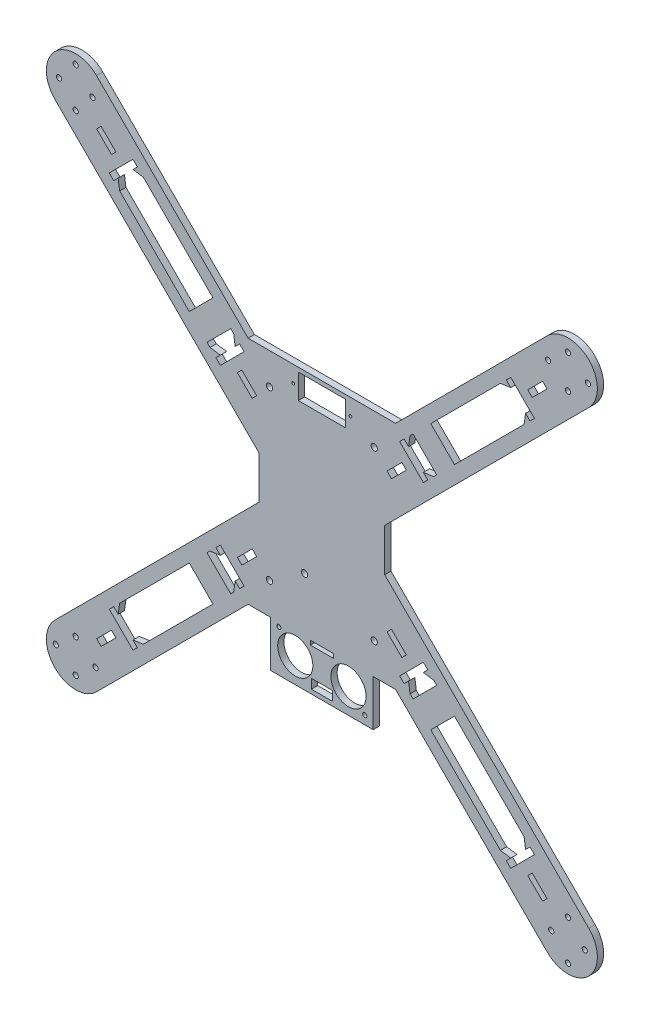
SolidWorks part; units mm, degrees
material "Custom Plastic"
ref_plane "Front Plane" through (0, 0, 0) normal (0, 0, 1) x (1, 0, 0)
ref_plane "Top Plane" through (0, 0, 0) normal (0, 1, 0) x (1, 0, 0)
ref_plane "Right Plane" through (0, 0, 0) normal (1, 0, 0) x (0, 0, -1)
sketch "Sketch1" plane through (0, 0, 0) normal (0, 0, 1) x (1, 0, 0)
  line L0 (117.5, 117.5) -> (-117.5, 117.5) construction
  line L1 (-117.5, 117.5) -> (117.5, -117.5) construction
  line L2 (117.5, -117.5) -> (-117.5, -117.5) construction
  line L3 (-117.5, -117.5) -> (117.5, 117.5) construction
  line L4 (117.5, 117.5) -> (117.5, -117.5) construction
  line L5 (-117.5, 117.5) -> (-117.5, -117.5) construction
  line L6 (0, 117.5) -> (0, -117.5) construction
  line L7 (35.201, 55) -> (-35.201, 55)
  line L8 (-30, 55) -> (30, 55) construction
  line L9 (-35.201, 55) -> (-107.6005, 127.3995)
  line L10 (-127.3995, 107.6005) -> (-30, 10.201)
  line L11 (-117.5, 0) -> (117.5, 0) construction
  line L12 (-30, 10.201) -> (-30, -10.201)
  line L13 (30, 55) -> (30, -55) construction
  line L14 (30, -55) -> (-30, -55) construction
  line L15 (-30, -55) -> (-30, 55) construction
  line L16 (30, 55) -> (-30, -55) construction
  line L17 (-24.5, -55) -> (-24.5, -77)
  line L18 (-127.3995, -107.6005) -> (-30, -10.201)
  line L19 (-24.5, -77) -> (24.5, -77)
  line L20 (-35.201, -55) -> (-107.6005, -127.3995)
  line L21 (35.201, -55) -> (24.5, -55)
  line L22 (35.201, -55) -> (107.6005, -127.3995)
  line L23 (127.3995, -107.6005) -> (30, -10.201)
  line L24 (30, 10.201) -> (30, -10.201)
  line L25 (127.3995, 107.6005) -> (30, 10.201)
  line L26 (35.201, 55) -> (107.6005, 127.3995)
  line L27 (24.5, -55) -> (24.5, -77)
  line L28 (-24.5, -55) -> (-35.201, -55)
  arc A0 (-107.6005, 127.3995) -> (-127.3995, 107.6005) centre (-117.5, 117.5) ccw
  arc A12 (-107.6005, -127.3995) -> (-127.3995, -107.6005) centre (-117.5, -117.5) cw
  arc A16 (107.6005, -127.3995) -> (127.3995, -107.6005) centre (117.5, -117.5) ccw
  arc A24 (107.6005, 127.3995) -> (127.3995, 107.6005) centre (117.5, 117.5) cw
  point P3 (0, 0)
  point P18 (0, 0)
  point P21 (0, -77)
  point P33 (-117.5, 117.5)
  point P34 (-30, 0)
  point P65 (0, -55)
  point P80 (0, 55)
  dimension "D3" = 14
  dimension "D8" = 24.5
  dimension "D7" = 22
  dimension "D1" = 235
  dimension "D2" = 235
  dimension "D4" = 60
  dimension "D5" = 110
  dimension "D6" = 28
extrude "Boss-Extrude1" add sketch "Sketch1" against normal blind 3
sketch "Sketch4" plane through (0, 0, 0) normal (0, 0, 1) x (1, 0, 0)
  line L0 (0, 0) -> (0, 55) construction
  line L1 (35.201, 55) -> (-35.201, 55) construction
  line L2 (0, 0) -> (-30, 0) construction
  line L3 (-30, 10.201) -> (-30, -10.201) construction
  line L4 (-30, 0) -> (-30, 10.201) construction
  line L5 (-30, 10.201) -> (-127.3995, 107.6005) construction
  line L6 (-35.201, 55) -> (-107.6005, 127.3995) construction
  line L7 (-107.6005, 127.3995) -> (-127.3995, 107.6005) construction
  line L8 (-117.5, 127) -> (-117.5, 108) construction
  line L9 (-125.5, 117.5) -> (-109.5, 117.5) construction
  circle A4 centre (-25, 40) radius 1.5
  circle A9 centre (-25, -40) radius 1.5
  circle A18 centre (25, -40) radius 1.5
  circle A19 centre (25, 40) radius 1.5
  circle A20 centre (-117.5, 127) radius 1.25
  circle A21 centre (-117.5, 108) radius 1.25
  circle A22 centre (-125.5, 117.5) radius 1.25
  circle A23 centre (-109.5, 117.5) radius 1.25
  circle A24 centre (117.5, 109.5) radius 1.25
  circle A25 centre (108, 117.5) radius 1.25
  circle A26 centre (117.5, 125.5) radius 1.25
  circle A27 centre (127, 117.5) radius 1.25
  circle A28 centre (109.5, -117.5) radius 1.25
  circle A29 centre (117.5, -108) radius 1.25
  circle A30 centre (125.5, -117.5) radius 1.25
  circle A31 centre (117.5, -127) radius 1.25
  circle A32 centre (-117.5, -109.5) radius 1.25
  circle A33 centre (-108, -117.5) radius 1.25
  circle A34 centre (-117.5, -125.5) radius 1.25
  circle A35 centre (-127, -117.5) radius 1.25
  point P16 (-117.5, 117.5)
  point P19 (-117.5, 117.5)
  point P26 (-117.5, 117.5)
  point P62 (0, 0)
  dimension "D1" = 45
  dimension "D6" = 3
  dimension "D4" = 2.5
  dimension "D2" = 19
  dimension "D7" = 15
  dimension "D8" = 5
  dimension "D3" = 16
extrude "Cut-Extrude1" cut sketch "Sketch4" against normal blind 3
sketch "Sketch5" plane through (0, 0, 0) normal (0, 0, 1) x (1, 0, 0)
  line L7 (-11.25, 53) -> (-11.25, 41.2)
  line L8 (-11.25, 41.2) -> (11.25, 41.2)
  line L9 (11.25, 41.2) -> (11.25, 53)
  line L10 (11.25, 53) -> (-11.25, 53)
  line L12 (0, 53) -> (0, 41.2) construction
  line L13 (-13.65, 47.1) -> (13.65, 47.1) construction
  line L14 (35.201, 55) -> (-35.201, 55) construction
  circle A2 centre (-13.65, 47.1) radius 0.65
  circle A3 centre (13.65, 47.1) radius 0.65
  point P20 (0, 47.1)
  point P21 (0, 47.1)
  point P26 (0, 55)
  dimension "D8" = 1.3
  dimension "D9" = 1.3
  dimension "D10" = 27.3
  dimension "D11" = 22.5
  dimension "D12" = 11.8
  dimension "D13" = 2
extrude "Cut-Extrude2" cut sketch "Sketch5" against normal blind 3
sketch "Sketch6" plane through (0, 0, 0) normal (0, 0, 1) x (1, 0, 0)
  line L1 (-11.25, 41.2) -> (11.25, 41.2) construction
  circle A0 centre (-8.25, -28.8) radius 1.5
  dimension "D3" = 3
  dimension "D1" = 70
  dimension "D2" = 3
extrude "Cut-Extrude3" cut sketch "Sketch6" against normal blind 3
sketch "Sketch7" plane through (0, 0, 0) normal (0, 0, 1) x (1, 0, 0)
  line L0 (-22.5, -55) -> (-22.5, -75) construction
  line L5 (-22.5, -75) -> (22.5, -75) construction
  line L6 (22.5, -75) -> (22.5, -55) construction
  line L7 (22.5, -55) -> (-22.5, -55) construction
  line L8 (0, -55) -> (0, -75) construction
  line L9 (-12.7, -65) -> (0, -65) construction
  line L10 (-24.5, -77) -> (24.5, -77) construction
  line L11 (-24.5, -55) -> (-24.5, -77) construction
  line L12 (-5.5, -55) -> (-5.5, -57)
  line L13 (-5.5, -57) -> (5.5, -57)
  line L15 (5.5, -55) -> (-5.5, -55)
  line L16 (-5, -75) -> (-5, -70.5)
  line L17 (-5, -70.5) -> (5, -70.5)
  line L21 (5, -75) -> (-5, -75)
  line L22 (5.5, -55) -> (5.5, -57)
  line L23 (5, -75) -> (5, -70.5)
  circle A5 centre (-20.5, -57) radius 1
  circle A6 centre (-12.7, -65) radius 8.4
  circle A7 centre (12.7, -65) radius 8.4
  circle A8 centre (20.5, -73) radius 1
  point P25 (0, -57)
  point P26 (0, -70.5)
  dimension "D3" = 2
  dimension "D6" = 20
  dimension "D13" = 5
  dimension "D5" = 45
  dimension "D1" = 2
  dimension "D4" = 16.8
  dimension "D14" = 2
  dimension "D2" = 2
  dimension "D7" = 2
  dimension "D8" = 2
  dimension "D9" = 12.7
  dimension "D10" = 5.5
  dimension "D11" = 2
  dimension "D12" = 4.5
  dimension "D15" = 2
  dimension "D16" = 2
extrude "Cut-Extrude4" cut sketch "Sketch7" against normal blind 3
sketch "Sketch8" plane through (0, 0, 0) normal (0, 0, 1) x (1, 0, 0)
  line L0 (101.4792, -90.1655) -> (90.1655, -101.4792)
  line L1 (90.1655, -101.4792) -> (88.0442, -99.3579)
  line L2 (37.1325, -48.4462) -> (48.4462, -37.1325)
  line L3 (48.4462, -37.1325) -> (50.5675, -39.2538)
  line L4 (105.7218, -85.9228) -> (85.9228, -105.7218) construction
  line L5 (127.3995, -107.6005) -> (30, -10.201) construction
  line L6 (35.201, -55) -> (107.6005, -127.3995) construction
  line L7 (40.3144, -38.1931) -> (38.1931, -40.3144)
  line L8 (117.5, -109.5) -> (109.5, -117.5) construction
  line L9 (38.1931, -40.3144) -> (31.1221, -33.2434)
  line L10 (50.5675, 39.2538) -> (48.4462, 37.1325)
  line L11 (31.1221, -33.2434) -> (33.2434, -31.1221)
  line L12 (33.2434, -31.1221) -> (40.3144, -38.1931)
  line L13 (42.7893, -42.7893) -> (39.2538, -39.2538) construction
  line L14 (35.201, -55) -> (107.6005, -127.3995) construction
  line L15 (100.4185, -98.2972) -> (98.2972, -100.4185)
  line L16 (98.2972, -100.4185) -> (105.3683, -107.4896)
  line L17 (105.3683, -107.4896) -> (107.4896, -105.3683)
  line L18 (107.4896, -105.3683) -> (100.4185, -98.2972)
  line L19 (99.3579, -99.3579) -> (95.8223, -95.8223) construction
  line L20 (-101.4792, -90.1655) -> (-99.3579, -88.0442)
  line L21 (-100.4185, -98.2972) -> (-107.4896, -105.3683)
  line L22 (-107.4896, -105.3683) -> (-105.3683, -107.4896)
  line L23 (-105.3683, -107.4896) -> (-98.2972, -100.4185)
  line L24 (-98.2972, -100.4185) -> (-100.4185, -98.2972)
  line L25 (-90.1655, -101.4792) -> (-101.4792, -90.1655)
  line L26 (-37.1325, -48.4462) -> (-39.2538, -50.5675)
  line L27 (-48.4462, -37.1325) -> (-37.1325, -48.4462)
  line L28 (-38.1931, -40.3144) -> (-40.3144, -38.1931)
  line L29 (-31.1221, -33.2434) -> (-38.1931, -40.3144)
  line L30 (-40.3144, -38.1931) -> (-33.2434, -31.1221)
  line L31 (-33.2434, -31.1221) -> (-31.1221, -33.2434)
  line L32 (-90.1655, 101.4792) -> (-88.0442, 99.3579)
  line L33 (-98.2972, 100.4185) -> (-105.3683, 107.4896)
  line L34 (-105.3683, 107.4896) -> (-107.4896, 105.3683)
  line L35 (-107.4896, 105.3683) -> (-100.4185, 98.2972)
  line L36 (-100.4185, 98.2972) -> (-98.2972, 100.4185)
  line L37 (-101.4792, 90.1655) -> (-90.1655, 101.4792)
  line L38 (-48.4462, 37.1325) -> (-50.5675, 39.2538)
  line L39 (-37.1325, 48.4462) -> (-48.4462, 37.1325)
  line L40 (-40.3144, 38.1931) -> (-38.1931, 40.3144)
  line L41 (-33.2434, 31.1221) -> (-40.3144, 38.1931)
  line L42 (-38.1931, 40.3144) -> (-31.1221, 33.2434)
  line L43 (-31.1221, 33.2434) -> (-33.2434, 31.1221)
  line L44 (101.4792, 90.1655) -> (99.3579, 88.0442)
  line L45 (100.4185, 98.2972) -> (107.4896, 105.3683)
  line L46 (107.4896, 105.3683) -> (105.3683, 107.4896)
  line L47 (105.3683, 107.4896) -> (98.2972, 100.4185)
  line L48 (98.2972, 100.4185) -> (100.4185, 98.2972)
  line L49 (90.1655, 101.4792) -> (101.4792, 90.1655)
  line L50 (37.1325, 48.4462) -> (39.2538, 50.5675)
  line L51 (48.4462, 37.1325) -> (37.1325, 48.4462)
  line L52 (38.1931, 40.3144) -> (40.3144, 38.1931)
  line L53 (31.1221, 33.2434) -> (38.1931, 40.3144)
  line L54 (40.3144, 38.1931) -> (33.2434, 31.1221)
  line L55 (33.2434, 31.1221) -> (31.1221, 33.2434)
  line L56 (30, 10.201) -> (127.3995, 107.6005) construction
  line L57 (42.0822, 53.3959) -> (85.2157, 96.5294)
  line L58 (96.5294, 85.2157) -> (53.3959, 42.0822)
  line L59 (88.0442, 99.3579) -> (90.1655, 101.4792)
  line L60 (99.3579, -88.0442) -> (97.2365, -90.1655)
  line L61 (-96.5294, -85.2157) -> (-53.3959, -42.0822)
  line L62 (97.2365, -90.1655) -> (96.5294, -85.2157)
  line L63 (99.3579, -88.0442) -> (101.4792, -90.1655)
  line L64 (88.0442, -99.3579) -> (90.1655, -97.2365)
  line L65 (-88.0442, -99.3579) -> (-90.1655, -101.4792)
  line L66 (90.1655, -97.2365) -> (85.2157, -96.5294)
  line L67 (85.2157, -96.5294) -> (42.0822, -53.3959)
  line L68 (50.5675, -39.2538) -> (48.4462, -41.3751)
  line L69 (48.4462, -41.3751) -> (53.3959, -42.0822)
  line L70 (53.3959, -42.0822) -> (96.5294, -85.2157)
  line L71 (39.2538, -50.5675) -> (41.3751, -48.4462)
  line L72 (41.3751, -48.4462) -> (42.0822, -53.3959)
  line L73 (39.2538, -50.5675) -> (37.1325, -48.4462)
  line L74 (-90.1655, -97.2365) -> (-85.2157, -96.5294)
  line L75 (-88.0442, -99.3579) -> (-90.1655, -97.2365)
  line L76 (-97.2365, -90.1655) -> (-96.5294, -85.2157)
  line L77 (-99.3579, -88.0442) -> (-97.2365, -90.1655)
  line L78 (-41.3751, -48.4462) -> (-42.0822, -53.3959)
  line L79 (-39.2538, -50.5675) -> (-41.3751, -48.4462)
  line L80 (-48.4462, -41.3751) -> (-53.3959, -42.0822)
  line L81 (-50.5675, -39.2538) -> (-48.4462, -41.3751)
  line L82 (-97.2365, 90.1655) -> (-96.5294, 85.2157)
  line L83 (-99.3579, 88.0442) -> (-97.2365, 90.1655)
  line L84 (-90.1655, 97.2365) -> (-85.2157, 96.5294)
  line L85 (-88.0442, 99.3579) -> (-90.1655, 97.2365)
  line L86 (-48.4462, 41.3751) -> (-53.3959, 42.0822)
  line L87 (-50.5675, 39.2538) -> (-48.4462, 41.3751)
  line L88 (-41.3751, 48.4462) -> (-42.0822, 53.3959)
  line L89 (-39.2538, 50.5675) -> (-41.3751, 48.4462)
  line L90 (90.1655, 97.2365) -> (85.2157, 96.5294)
  line L91 (88.0442, 99.3579) -> (90.1655, 97.2365)
  line L92 (97.2365, 90.1655) -> (96.5294, 85.2157)
  line L93 (99.3579, 88.0442) -> (97.2365, 90.1655)
  line L94 (41.3751, 48.4462) -> (42.0822, 53.3959)
  line L95 (39.2538, 50.5675) -> (41.3751, 48.4462)
  line L96 (48.4462, 41.3751) -> (53.3959, 42.0822)
  line L97 (50.5675, 39.2538) -> (48.4462, 41.3751)
  line L98 (-39.2538, 50.5675) -> (-37.1325, 48.4462)
  line L99 (-53.3959, 42.0822) -> (-96.5294, 85.2157)
  line L100 (-99.3579, 88.0442) -> (-101.4792, 90.1655)
  line L101 (-85.2157, 96.5294) -> (-42.0822, 53.3959)
  line L102 (-42.0822, -53.3959) -> (-85.2157, -96.5294)
  line L103 (-50.5675, -39.2538) -> (-48.4462, -37.1325)
  point P10 (95.8223, -95.8223)
  point P11 (95.8223, -95.8223)
  point P68 (0, 0)
  point P122 (0, 0)
  dimension "D1" = 25
  dimension "D2" = 75
  dimension "D3" = 3
  dimension "D4" = 10
  dimension "D5" = 5
  dimension "D6" = 6
  dimension "D7" = 3
  dimension "D8" = 10
  dimension "D9" = 5
  dimension "D11" = 6
  dimension "D12" = 3
  dimension "D13" = 4
  dimension "D14" = 3
  dimension "D15" = 3
  dimension "D16" = 4
  dimension "D17" = 3
  dimension "D18" = 3
  dimension "D19" = 4
  dimension "D20" = 3
  dimension "D21" = 3
  dimension "D22" = 4
  dimension "D23" = 3
  dimension "D10" = 4
extrude "Cut-Extrude5" cut sketch "Sketch8" against normal through all
sketch "Sketch9" plane through (-5.6569, 5.6569, 0) normal (0.7071, -0.7071, 0) x (0, 0, -1)
  line L0 (3, 128.5132) -> (3, 67.5132) construction
  line L1 (3, 81.5132) -> (0, 81.5132)
  line L2 (3, 81.5132) -> (3, 69.5132)
  line L3 (3, 69.5132) -> (0, 69.5132)
  line L4 (0, 81.5132) -> (0, 69.5132)
  line L5 (0, 128.5132) -> (0, 67.5132) construction
  line L6 (0, 0) -> (28.0274, 0) construction
  line L7 (3, 63.5132) -> (0, 63.5132) construction
  dimension "D1" = 6
  dimension "D2" = 12
extrude "Boss-Extrude2" add sketch "Sketch9" along normal up to next
sketch "Sketch11" plane through (5.6569, 5.6569, 0) normal (-0.7071, -0.7071, 0) x (0, 0, 1)
  line L0 (-3, -128.5132) -> (-3, -67.5132) construction
  line L1 (-3, -69.5132) -> (0, -69.5132)
  line L2 (-3, -69.5132) -> (-3, -81.5132)
  line L3 (-3, -81.5132) -> (0, -81.5132)
  line L4 (0, -69.5132) -> (0, -81.5132)
  line L5 (0, -128.5132) -> (0, -67.5132) construction
  line L6 (-3, -63.5132) -> (0, -63.5132) construction
  dimension "D1" = 6
  dimension "D2" = 12
extrude "Boss-Extrude3" add sketch "Sketch11" along normal up to next
sketch "Sketch12" plane through (5.6569, -5.6569, 0) normal (-0.7071, 0.7071, 0) x (0, 0, 1)
  line L0 (-3, -128.5132) -> (-3, -67.5132) construction
  line L1 (-3, -69.5132) -> (0, -69.5132)
  line L2 (-3, -69.5132) -> (-3, -81.5132)
  line L3 (-3, -81.5132) -> (0, -81.5132)
  line L4 (0, -69.5132) -> (0, -81.5132)
  line L5 (0, -128.5132) -> (0, -67.5132) construction
  dimension "D1" = 6
  dimension "D2" = 12
extrude "Boss-Extrude4" add sketch "Sketch12" along normal up to next
sketch "Sketch13" plane through (5.6569, 5.6569, 0) normal (-0.7071, -0.7071, 0) x (0, 0, 1)
  line L0 (-3, 67.5132) -> (-3, 128.5132) construction
  line L1 (-3, 69.5132) -> (0, 69.5132)
  line L2 (-3, 69.5132) -> (-3, 81.5132)
  line L3 (-3, 81.5132) -> (0, 81.5132)
  line L4 (0, 69.5132) -> (0, 81.5132)
  line L5 (0, 67.5132) -> (0, 128.5132) construction
  dimension "D1" = 6
  dimension "D2" = 12
extrude "Boss-Extrude5" add sketch "Sketch13" along normal up to next
